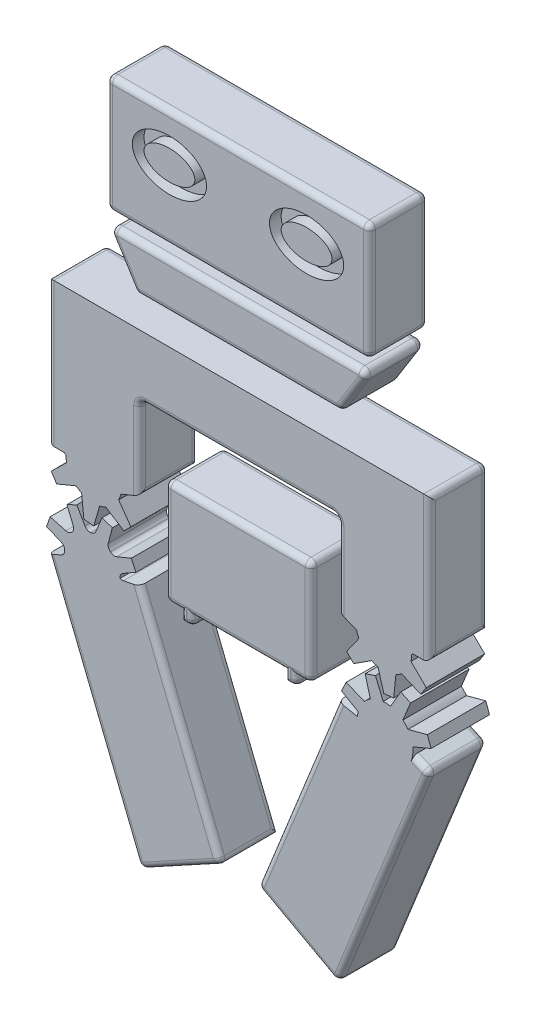
SolidWorks part; units mm, degrees
ref_plane "Front Plane" through (0, 0, 0) normal (0, 0, 1) x (1, 0, 0)
ref_plane "Top Plane" through (0, 0, 0) normal (0, 1, 0) x (1, 0, 0)
ref_plane "Right Plane" through (0, 0, 0) normal (1, 0, 0) x (0, 0, -1)
sketch "Sketch1" plane through (0, 0, 0) normal (0, 0, 1) x (1, 0, 0)
  line L0 (0, 0) -> (0, 38.9596) construction
  line L1 (0, 80) -> (65.261, 80)
  line L2 (0, 0) -> (65.261, 0) construction
  line L3 (65.261, 0) -> (65.261, 38.9596) construction
  line L4 (19.4871, 80) -> (19.4871, 69.3455) construction
  line L5 (32.6305, 69.3455) -> (32.6305, 0) construction
  line L6 (49.6065, 41.9925) -> (35.7458, 7.564)
  line L7 (15.6545, 55.3839) -> (15.6545, 69.3455)
  line L8 (15.6545, 69.3455) -> (49.6065, 69.3455)
  line L9 (49.6065, 69.3455) -> (49.6065, 55.3839)
  line L10 (65, 41.9925) -> (42.5556, 41.9925) construction
  line L11 (0, 55.3839) -> (0, 80)
  line L12 (0, 41.9925) -> (0, 85) construction
  line L13 (65.261, 80) -> (65.261, 55.3839)
  line L14 (65.261, 38.9596) -> (49.5762, 0)
  line L15 (0, 85) -> (65.261, 85) construction
  line L16 (65.261, 85) -> (65.261, 38.9596) construction
  line L17 (65.261, 38.9596) -> (50.2677, 1.7176) construction
  line L18 (35.7458, 7.564) -> (49.5762, 0)
  line L19 (29.5152, 7.564) -> (15.6848, 0)
  line L20 (0, 38.9596) -> (15.6848, 0)
  line L21 (15.6545, 41.9925) -> (29.5152, 7.564)
  line L22 (0, 55.3839) -> (2.7557, 55.3839) construction
  line L24 (49.6065, 55.3839) -> (65.261, 55.3839) construction
  line L25 (65.261, 55.3839) -> (65.261, 80) construction
  line L26 (0, 55.3839) -> (0, 38.9596) construction
  line L27 (15.6545, 41.9925) -> (15.6545, 69.3455) construction
  line L28 (49.6065, 69.3455) -> (49.6065, 41.9925) construction
  line L29 (65.261, 55.3839) -> (65.261, 38.9596) construction
  line L30 (12.3305, 41.3485) -> (15.6545, 41.9925) construction
  line L31 (4.5632, 44.7158) -> (3.2456, 47.9048)
  line L32 (3.2456, 47.9048) -> (4.921, 48.7132)
  line L33 (4.921, 48.7132) -> (6.6566, 45.7095)
  line L34 (7.93, 45.7819) -> (9.2533, 48.9685)
  line L35 (9.2533, 48.9685) -> (11.0097, 48.3554)
  line L36 (11.0097, 48.3554) -> (10.1276, 45.0591)
  line L37 (11.1488, 44.1898) -> (14.2536, 45.4725)
  line L38 (14.2536, 45.4725) -> (15.062, 43.7971)
  line L39 (15.062, 43.7971) -> (12.2098, 42.1491)
  line L40 (15.0603, 44.2263) -> (15.0632, 44.2267)
  line L41 (5.5184, 50.9884) -> (5.4969, 51.0004)
  line L42 (6.1306, 47.2078) -> (5.7544, 50.8659)
  line L43 (6.1306, 47.2078) -> (7.8273, 47.0285)
  line L44 (7.8273, 47.0285) -> (8.8264, 50.4968)
  line L45 (0.5602, 51.5245) -> (3.1858, 54.0994)
  line L46 (0.5602, 51.5245) -> (1.478, 50.0862)
  line L47 (1.478, 50.0862) -> (4.8126, 51.4675)
  line L48 (2.7557, 55.3839) -> (3.0688, 55.2108)
  line L50 (2.905, 40.2479) -> (2.8978, 40.2447)
  line L51 (0.828, 36.9029) -> (0.8133, 36.8968)
  line L52 (65.261, 55.3839) -> (62.5054, 55.3839) construction
  line L53 (51.0845, 50.0862) -> (53.1731, 53.0298)
  line L54 (2.8717, 41.608) -> (-0.2504, 42.9046)
  line L55 (-0.2504, 42.9046) -> (0.3627, 44.6609)
  line L56 (0.3627, 44.6609) -> (3.6896, 43.7707)
  line L58 (0, 55.3839) -> (2.7557, 55.3839)
  line L59 (12.3305, 41.3485) -> (15.6545, 41.9925)
  line L60 (52.2824, 48.8714) -> (51.0845, 50.0862)
  line L61 (52.2824, 48.8714) -> (55.377, 50.8582)
  line L62 (0.0037, 38.1427) -> (0, 38.1548)
  line L63 (49.6065, 55.3839) -> (52.7962, 54.082)
  line L64 (15.6545, 55.3839) -> (12.4648, 54.082)
  line L65 (65.261, 55.3839) -> (62.5054, 55.3839)
  line L66 (62.5054, 55.3839) -> (62.1922, 55.2108)
  line L67 (63.783, 50.0862) -> (60.4484, 51.4675)
  line L68 (64.7008, 51.5245) -> (63.783, 50.0862)
  line L69 (64.7008, 51.5245) -> (62.0753, 54.0994)
  line L70 (57.4338, 47.0285) -> (56.4346, 50.4968)
  line L71 (59.1304, 47.2078) -> (57.4338, 47.0285)
  line L72 (59.1304, 47.2078) -> (59.5066, 50.8659)
  line L73 (59.7426, 50.9884) -> (59.7641, 51.0004)
  line L74 (54.2513, 48.3554) -> (55.1334, 45.0591)
  line L75 (56.0077, 48.9685) -> (54.2513, 48.3554)
  line L76 (57.331, 45.7819) -> (56.0077, 48.9685)
  line L77 (60.34, 48.7132) -> (58.6044, 45.7095)
  line L78 (62.0154, 47.9048) -> (60.34, 48.7132)
  line L79 (60.6979, 44.7158) -> (62.0154, 47.9048)
  line L80 (52.9305, 41.3485) -> (49.6065, 41.9925)
  line L81 (50.199, 43.7971) -> (53.0512, 42.1491)
  line L82 (51.0074, 45.4725) -> (50.199, 43.7971)
  line L83 (54.1122, 44.1898) -> (51.0074, 45.4725)
  line L84 (64.8983, 44.6609) -> (61.5714, 43.7707)
  line L85 (65.5114, 42.9046) -> (64.8983, 44.6609)
  line L86 (62.3893, 41.608) -> (65.5114, 42.9046)
  line L87 (62.356, 40.2479) -> (65.261, 38.9596)
  line L88 (20, 60) -> (45, 60)
  line L89 (20, 60) -> (20, 41.9925)
  line L90 (45, 60) -> (45, 41.9925)
  line L91 (4.0572, 34.0139) -> (4.9539, 37.3651) [skipped]
  line L92 (7.1369, 36.5874) -> (5.8136, 33.4008) [skipped]
  line L93 (10.1459, 33.6561) -> (8.4103, 36.6598) [skipped]
  line L94 (10.5038, 37.6535) -> (11.8213, 34.4645) [skipped]
  line L95 (14.7042, 37.7085) -> (11.3531, 38.6052) [skipped]
  line L96 (12.1307, 40.7881) -> (15.3173, 39.4648) [skipped]
  line L97 (5.8136, 33.4008) -> (4.0572, 34.0139) [skipped]
  line L98 (11.8213, 34.4645) -> (10.1459, 33.6561) [skipped]
  line L99 (15.3173, 39.4648) -> (14.7042, 37.7085) [skipped]
  line L100 (45, 41.9925) -> (42.5556, 41.9925)
  line L101 (22.7054, 41.9925) -> (22.7054, 40.2479)
  line L102 (12.9786, 48.8714) -> (9.884, 50.8582)
  line L103 (12.9786, 48.8714) -> (14.1765, 50.0862)
  line L104 (14.1765, 50.0862) -> (12.0879, 53.0298)
  line L105 (4.3037, 62.4664) -> (4.9083, 58.908) [skipped]
  line L106 (5.9101, 63.0411) -> (7.8362, 59.9084) [skipped]
  line L107 (11.3508, 62.4664) -> (8.9458, 59.7751) [skipped]
  line L108 (12.8017, 61.5688) -> (11.5534, 58.1097) [skipped]
  line L109 (0.4621, 58.571) -> (4.1122, 58.1236) [skipped]
  line L110 (15.9475, 55.2627) -> (12.4648, 54.082) [skipped]
  line L111 (15.9475, 55.2627) -> (15.7447, 56.9567) [skipped]
  line L112 (15.7447, 56.9567) -> (15.6545, 56.9618) [skipped]
  line L113 (12.8017, 61.5688) -> (11.3508, 62.4664) [skipped]
  line L114 (5.9101, 63.0411) -> (4.3037, 62.4664) [skipped]
  line L115 (0.8133, 36.8968) -> (0.4027, 37.7477) [skipped]
  line L116 (0.0049, 38.5722) -> (3.0086, 40.3078) [skipped]
  line L117 (24.8007, 40.2479) -> (22.7054, 40.2479)
  line L118 (24.8007, 41.9925) -> (24.8007, 40.2479)
  line L119 (40.4603, 41.9925) -> (40.4603, 40.2479)
  line L120 (40.4603, 40.2479) -> (42.5556, 40.2479)
  line L121 (42.5556, 41.9925) -> (42.5556, 40.2479)
  line L122 (22.7054, 41.9925) -> (13.8344, 41.9925) construction
  line L123 (22.7054, 41.9925) -> (20, 41.9925)
  line L124 (40.4603, 41.9925) -> (24.8007, 41.9925) construction
  line L125 (40.4603, 41.9925) -> (24.8007, 41.9925)
  line L126 (10, 115) -> (10, 95)
  line L127 (10, 115) -> (55, 115)
  line L128 (55, 115) -> (55, 95)
  line L129 (55, 95) -> (10, 95)
  line L130 (0, 38.9596) -> (2.8978, 40.2447)
  line L131 (10, 93) -> (55, 93)
  line L132 (55, 93) -> (50, 85)
  line L133 (50, 85) -> (15, 85)
  line L134 (15, 85) -> (10, 93)
  line L136 (0, 57.2203) -> (-0.0902, 56.9567) [skipped]
  line L137 (-0.0902, 56.9567) -> (0, 56.9069) [skipped]
  arc A3 (4.921, 48.7132) -> (3.2456, 47.9048) centre (7.5892, 41.043) ccw construction
  arc A5 (3.0688, 55.2108) -> (3.1858, 54.0994) centre (7.8273, 55.1496) ccw construction
  arc A6 (12.3381, 41.35) -> (12.2167, 42.1531) centre (7.5892, 41.043) ccw construction
  arc A7 (0.5602, 51.5245) -> (1.478, 50.0862) centre (7.8273, 55.1496) ccw construction
  arc A8 (12.9786, 48.8714) -> (14.1765, 50.0862) centre (7.8273, 55.1496) ccw construction
  arc A9 (3.6853, 48.1642) -> (3.7294, 48.1383) centre (7.8273, 55.1496) ccw construction
  arc A10 (3.6896, 43.7707) -> (4.5632, 44.7158) centre (7.5892, 41.043) cw
  arc A11 (3.0688, 55.2108) -> (3.1858, 54.0994) centre (7.8273, 55.1496) ccw
  arc A12 (0, 38.1523) -> (0.0037, 38.1427) centre (7.5892, 41.043) ccw construction
  arc A13 (4.8126, 51.4675) -> (5.7544, 50.8659) centre (7.8273, 55.1496) ccw construction
  arc A14 (4.8126, 51.4675) -> (5.7544, 50.8659) centre (7.8273, 55.1496) ccw
  arc A15 (8.8264, 50.4968) -> (9.884, 50.8582) centre (7.8273, 55.1496) ccw construction
  arc A16 (8.8264, 50.4968) -> (9.884, 50.8582) centre (7.8273, 55.1496) ccw
  arc A17 (12.0879, 53.0298) -> (12.4648, 54.082) centre (7.8273, 55.1496) ccw construction
  arc A18 (12.0879, 53.0298) -> (12.4648, 54.082) centre (7.8273, 55.1496) ccw
  arc A19 (12.3305, 41.3485) -> (12.2098, 42.1491) centre (7.5892, 41.043) ccw
  arc A20 (11.1488, 44.1898) -> (10.1276, 45.0591) centre (7.5892, 41.043) ccw
  arc A21 (11.1563, 44.1929) -> (10.1297, 45.0669) centre (7.5892, 41.043) ccw construction
  arc A22 (2.8717, 41.608) -> (2.905, 40.2479) centre (7.5892, 41.043) ccw
  arc A23 (7.9331, 45.7894) -> (6.6566, 45.7095) centre (7.5892, 41.043) ccw construction
  arc A24 (4.5632, 44.7158) -> (3.6896, 43.7707) centre (7.5892, 41.043) ccw construction
  arc A25 (2.8644, 41.6111) -> (2.8979, 40.2438) centre (7.5892, 41.043) ccw construction
  arc A26 (6.6566, 45.7095) -> (7.9331, 45.7894) centre (7.5892, 41.043) cw
  arc A27 (57.3279, 45.7894) -> (58.6044, 45.7095) centre (57.6719, 41.043) cw construction
  arc A28 (53.1731, 53.0298) -> (52.7962, 54.082) centre (57.4338, 55.1496) cw construction
  arc A29 (56.4346, 50.4968) -> (55.377, 50.8582) centre (57.4338, 55.1496) cw construction
  arc A30 (60.4484, 51.4675) -> (59.5066, 50.8659) centre (57.4338, 55.1496) cw construction
  arc A31 (61.5757, 48.1642) -> (61.5316, 48.1383) centre (57.4338, 55.1496) cw construction
  arc A32 (52.2824, 48.8714) -> (51.0845, 50.0862) centre (57.4338, 55.1496) cw construction
  arc A33 (64.7008, 51.5245) -> (63.783, 50.0862) centre (57.4338, 55.1496) cw construction
  arc A34 (62.1922, 55.2108) -> (62.0753, 54.0994) centre (57.4338, 55.1496) cw construction
  arc A35 (60.34, 48.7132) -> (62.0154, 47.9048) centre (57.6719, 41.043) cw construction
  arc A36 (58.6044, 45.7095) -> (57.3279, 45.7894) centre (57.6719, 41.043) ccw
  arc A37 (53.1731, 53.0298) -> (52.7962, 54.082) centre (57.4338, 55.1496) cw
  arc A38 (56.4346, 50.4968) -> (55.377, 50.8582) centre (57.4338, 55.1496) cw
  arc A39 (60.4484, 51.4675) -> (59.5066, 50.8659) centre (57.4338, 55.1496) cw
  arc A40 (62.1922, 55.2108) -> (62.0753, 54.0994) centre (57.4338, 55.1496) cw
  arc A41 (52.9305, 41.3485) -> (53.0512, 42.1491) centre (57.6719, 41.043) cw
  arc A42 (54.1122, 44.1898) -> (55.1334, 45.0591) centre (57.6719, 41.043) cw
  arc A43 (62.3893, 41.608) -> (62.356, 40.2479) centre (57.6719, 41.043) cw
  arc A45 (60.6979, 44.7158) -> (61.5714, 43.7707) centre (57.6719, 41.043) cw
  point P68 (7.5335, 41.1847)
  point P82 (7.5335, 41.1847)
  point P104 (57.4338, 55.1496)
  point P158 (7.8273, 55.1496)
  dimension "D1" = 8
  dimension "D2" = 7
extrude "Boss-Extrude1" add sketch "Sketch1" along normal blind 10 contours A45 L79 L78 L77 A36 L76 L75 L74 A42 L83 L82 L81 A41 L80 L6 L18 L14 L87 A43 L86 L85 L84 | A40 L66 L65 L13 L1 L11 L58 L48 A11 L45 L46 L47 A14 L41 L42 L43 L44 A16 L102 L103 L104 A18 L64 L7 L8 L9 L63 A37 L53 L60 L61 A38 L70 L71 L72 A39 L73 L67 L68 L69 | A26 L33 L32 L31 A10 L56 L55 L54 A22 L50 L130 L20 L19 L21 L59 A19 L39 L38 L37 A20 L36 L35 L34 | L134 L133 L132 L131 | L129 L128 L127 L126 | L125 L119 L120 L121 L100 L90 L88 L89 L123 L101 L117 L118 region at (32.6305, 79.2688, 0) region at (50.9973, 24.261, 0) region at (14.2742, 24.2492, 0) region at (1.0108, 39.2835, 0) region at (32.5021, 50.8384, 0) region at (32.5, 105, 0) region at (32.5, 89.1667, 0)
sketch "Sketch2" plane through (0, 0, 10) normal (0, 0, 1) x (1, 0, 0)
  ellipse E0 centre (20.7694, 106.9534) end of major axis (27.1176, 106.9534) minor radius 4.3435
  ellipse E1 centre (20.7694, 106.9534) end of major axis (25.1129, 106.9534) minor radius 2.5059
  ellipse E2 centre (44.2306, 106.9534) end of major axis (39.8871, 106.9534) minor radius 2.5059
  ellipse E3 centre (44.2306, 106.9534) end of major axis (37.8824, 106.9534) minor radius 4.3435
  point P0 (0, 0)
fillet "Fillet1" radius 1 1 edges at (6.6566, 45.7095, 5)
fillet "Fillet2" radius 1 1 edges at (11.1488, 44.1898, 5)
fillet "Fillet3" radius 1 1 edges at (10.1276, 45.0591, 5)
fillet "Fillet4" radius 1 1 edges at (12.2098, 42.1491, 5)
fillet "Fillet5" radius 1 1 edges at (12.3305, 41.3485, 5)
fillet "Fillet6" radius 1 1 edges at (2.8717, 41.608, 5)
fillet "Fillet7" radius 1 1 edges at (2.905, 40.2479, 5)
fillet "Fillet8" radius 1 1 edges at (4.5632, 44.7158, 5)
fillet "Fillet9" radius 1 1 edges at (7.9331, 45.7894, 5)
fillet "Fillet10" radius 1 1 edges at (3.6896, 43.7707, 5)
fillet "Fillet13" radius 1 7 edges at (7.8424, 19.4798, 0) (22.5848, 24.7782, 0) (15.6848, 0, 5) (22.6, 3.782, 10) (29.5152, 7.564, 5) (7.8424, 19.4798, 10) (22.5848, 24.7782, 10)
fillet "Fillet14" radius 1 11 edges at (49.5762, 0, 5) (57.4186, 19.4798, 10) (65.261, 38.9596, 5) (57.4186, 19.4798, 0) (63.8085, 39.6038, 0) (63.8085, 39.6038, 10) (42.661, 3.782, 0) (35.7458, 7.564, 5) (42.6762, 24.7782, 0) (42.661, 3.782, 10) (42.6762, 24.7782, 10)
fillet "Fillet15" radius 1 18 edges at (32.6305, 69.3455, 10) (32.6305, 69.3455, 0) (15.6545, 55.3839, 5) (15.6545, 62.3647, 10) (15.6545, 69.3455, 5) (15.6545, 62.3647, 0) (49.6065, 69.3455, 5) (65.261, 55.3839, 5) (0, 55.3839, 5) (0, 67.6919, 10) (65.261, 67.6919, 10) (49.6065, 62.3647, 10) (49.6065, 62.3647, 0) (0, 67.6919, 0) (0, 80, 5) (32.6305, 80, 0) (65.261, 80, 5) (65.261, 67.6919, 0)
fillet "Fillet17" radius 1 12 edges at (45, 60, 5) (32.5, 60, 10) (20, 60, 5) (32.5, 60, 0) (32.6305, 41.9925, 0) (45, 50.9963, 0) (45, 41.9925, 5) (32.6305, 41.9925, 10) (20, 41.9925, 5) (20, 50.9963, 0) (45, 50.9963, 10) (20, 50.9963, 10)
fillet "Fillet18" radius 1 12 edges at (20.2929, 42.2854, 9.7071) (44.7071, 42.2854, 9.7071) (23.7531, 40.2479, 10) (22.7054, 41.1202, 10) (21.8527, 41.9925, 10) (43.2778, 41.9925, 10) (42.5556, 41.1202, 10) (41.5079, 40.2479, 10) (40.4603, 41.6202, 10) (24.8007, 41.6202, 10) (42.5556, 40.2479, 5) (24.8007, 40.2479, 5)
fillet "Fillet19" radius 1 12 edges at (10, 105, 10) (32.5, 115, 10) (55, 105, 10) (32.5, 95, 10) (55, 95, 5) (55, 115, 5) (10, 115, 5) (10, 95, 5) (10, 105, 0) (32.5, 115, 0) (55, 105, 0) (32.5, 95, 0)
fillet "Fillet20" radius 1 12 edges at (32.5, 93, 10) (52.5, 89, 10) (32.5, 85, 10) (12.5, 89, 10) (32.5, 93, 0) (55, 93, 5) (52.5, 89, 0) (15, 85, 5) (50, 85, 5) (10, 93, 5) (32.5, 85, 0) (12.5, 89, 0)
extrude "Cut-Extrude1" cut sketch "Sketch2" against normal blind 2
